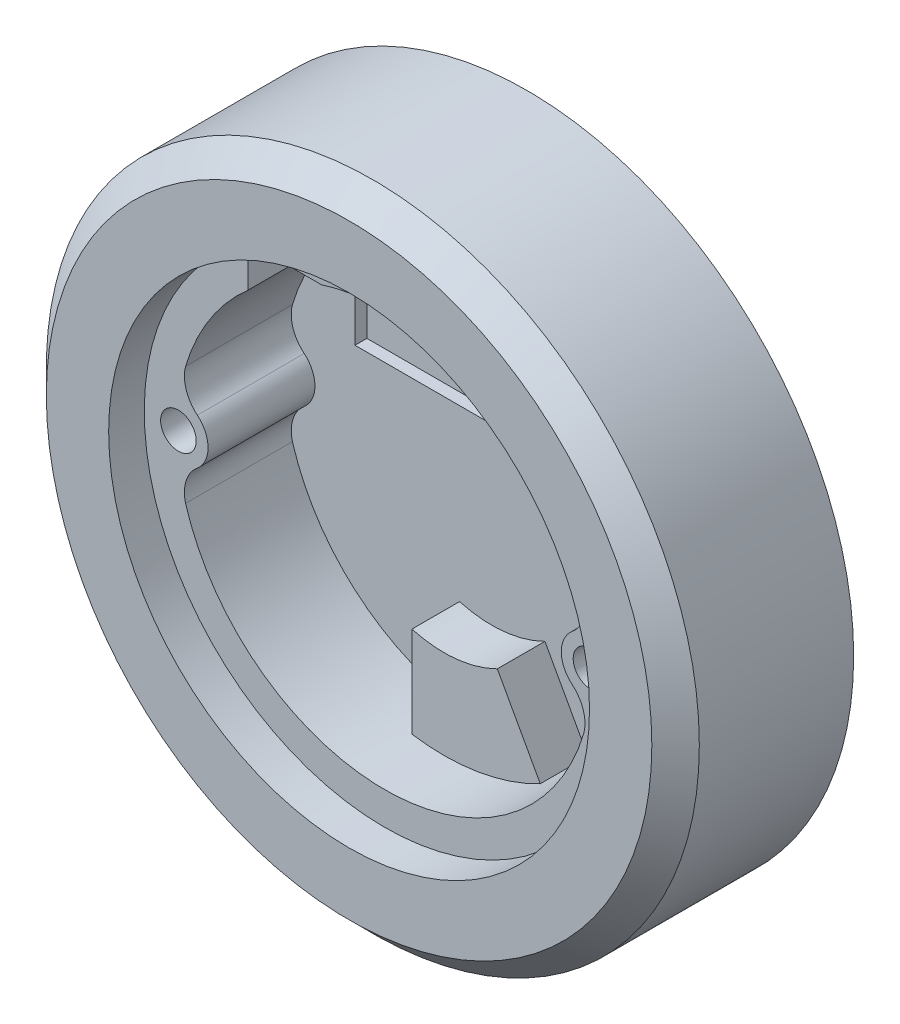
SolidWorks part; units mm, degrees
ref_plane "Front Plane" through (0, 0, 0) normal (0, 0, 1) x (1, 0, 0)
ref_plane "Top Plane" through (0, 0, 0) normal (0, 1, 0) x (1, 0, 0)
ref_plane "Right Plane" through (0, 0, 0) normal (1, 0, 0) x (0, 0, -1)
sketch "Sketch1" plane through (0, 0, 0) normal (0, 0, 1) x (1, 0, 0)
  circle A0 centre (0, 0) radius 27.5
  dimension "D1" = 55
extrude "Boss-Extrude1" add sketch "Sketch1" along normal blind 15
chamfer "Chamfer1" distance 2 angle 45 1 edges at (27.5, 0, 15)
sketch "Sketch2" plane through (0, 0, 15) normal (0, 0, 1) x (1, 0, 0)
  circle A0 centre (0, 0) radius 17.5
  dimension "D1" = 35
extrude "Cut-Extrude1" cut sketch "Sketch2" against normal blind 12
sketch "Sketch3" plane through (0, 0, 15) normal (0, 0, 1) x (1, 0, 0)
  circle A0 centre (0, 0) radius 20.25
  dimension "D1" = 40.5
extrude "Cut-Extrude2" cut sketch "Sketch3" against normal blind 3
sketch "Sketch4" plane through (0, 0, 0) normal (0, 1, 0) x (1, 0, 0)
  line L0 (-17.5, -3) -> (17.5, -3) construction
  circle A0 centre (0, -5) radius 2
  dimension "D1" = 4
  dimension "D2" = 2
extrude "Cut-Extrude3" cut sketch "Sketch4" against normal through all contours A0
sketch "Sketch5" plane through (0, 0, 12) normal (0, 0, 1) x (1, 0, 0)
  line L0 (8.25, 0) -> (-8.25, 0) construction
  line L1 (-17.0821, 0) -> (-9.1931, 0) construction
  arc A0 (-15.7814, -1.9262) -> (-15.7814, 1.9262) centre (-17.375, 0) ccw
  arc A1 (-15.7814, -1.9262) -> (-16.7705, -5) centre (-13.869, -4.2377) ccw
  circle A2 centre (0, 0) radius 17.5 construction
  arc A3 (-15.7814, 1.9262) -> (-16.7705, 5) centre (-13.869, 4.2377) cw
  arc A4 (-16.7705, -5) -> (-16.7705, 5) centre (0, 0) cw
  point P1 (0, 0)
  dimension "D1" = 5
  dimension "D4" = 3
  dimension "D2" = 17.375
  dimension "D3" = 5
extrude "Boss-Extrude2" add sketch "Sketch5" against normal up to surface (9 mm away) up to face at (17.5, 0, 3)
sketch "Sketch6" plane through (0, 0, 12) normal (0, 0, 1) x (1, 0, 0)
  circle A0 centre (-17.375, 0) radius 1.5
  dimension "D1" = 3
extrude "Cut-Extrude4" cut sketch "Sketch6" against normal through all
chamfer "Chamfer2" distance 2 angle 45 1 edges at (-15.875, 0, 0)
mirror "Mirror1" about plane through (0, 0, 0) normal (1, 0, 0) of "Chamfer2", "Boss-Extrude2", "Cut-Extrude4"
sketch "Sketch8" plane through (0, 0, 3) normal (0, 0, 1) x (1, 0, 0)
  line L0 (0, -17.5) -> (0, 0) construction
  line L2 (-2.6967, -17.291) -> (-2.6967, -9.6295)
  line L4 (4.4954, -8.9326) -> (8.1141, -15.5052) construction
  line L5 (8.1141, -15.5052) -> (4.4954, -8.9326)
  arc A0 (-2.6967, -17.291) -> (8.1141, -15.5052) centre (0, 0) ccw
  arc A1 (-16.7705, -5) -> (0, -17.5) centre (0, 0) ccw construction
  arc A2 (-2.6967, -9.6295) -> (4.4954, -8.9326) centre (0, 0) ccw
  dimension "D3" = 10
extrude "Boss-Extrude8" add sketch "Sketch8" along normal blind 4.01
ref_plane "Plane1" through (0, 0, 5.01) normal (0, 0, 1) x (1, 0, 0)
ref_axis "Axis1" [suppressed] through (0, 30.25, 7.01) along (0, -1, 0)
sketch "Sketch10" plane through (0, 0, 5.01) normal (0, 0, 1) x (1, 0, 0)
  line L0 (0, -29.9582) -> (0, -15.8745) construction
  arc A1 (1.75, -13.8902) -> (9.4717, -10.3096) centre (0, 0) ccw construction
  arc A2 (1.75, -13.8902) -> (0, -15.8745) centre (2, -15.8745) ccw construction
  point P0 (5.8896, -12.7009)
  dimension "D1" = 2
  dimension "D2" = 14
sketch "Sketch13" plane through (-0.3243, -0.1785, 0) normal (0.876, 0.4823, 0) x (0, 0, -1)
  line L0 (-3, -17.4961) -> (-3, -9.9931) construction
  line L1 (-5, -16) -> (-7.01, -16)
  line L2 (-7.01, -17.4961) -> (-7.01, -9.9931) construction
  line L3 (-7.01, -16) -> (-7.01, -12)
  line L4 (-7.01, -12) -> (-5, -12)
  arc A0 (-5, -16) -> (-5, -12) centre (-5, -14) ccw
  dimension "D1" = 14
  dimension "D2" = 4
  dimension "D3" = 2
sketch "Sketch14" plane through (0, 0, 12) normal (0, 0, 1) x (1, 0, 0)
  line L1 (-11.5, 16.6677) -> (11.5, 16.6677)
  line L2 (-11.5, 16.6677) -> (-11.5, 4.6677)
  line L3 (-11.5, 4.6677) -> (11.5, 4.6677)
  line L4 (11.5, 16.6677) -> (11.5, 4.6677)
  circle A0 centre (0, 0) radius 20.25 construction
  circle A1 centre (0, 0) radius 20.25 construction
  point P6 (0, 0)
  dimension "D1" = 23
  dimension "D2" = 12
extrude "Cut-Extrude5" cut sketch "Sketch14" against normal offset from surface (10 mm away) 1 up to face at (0.5472, -3.5369, 3) offset beyond the face yes
